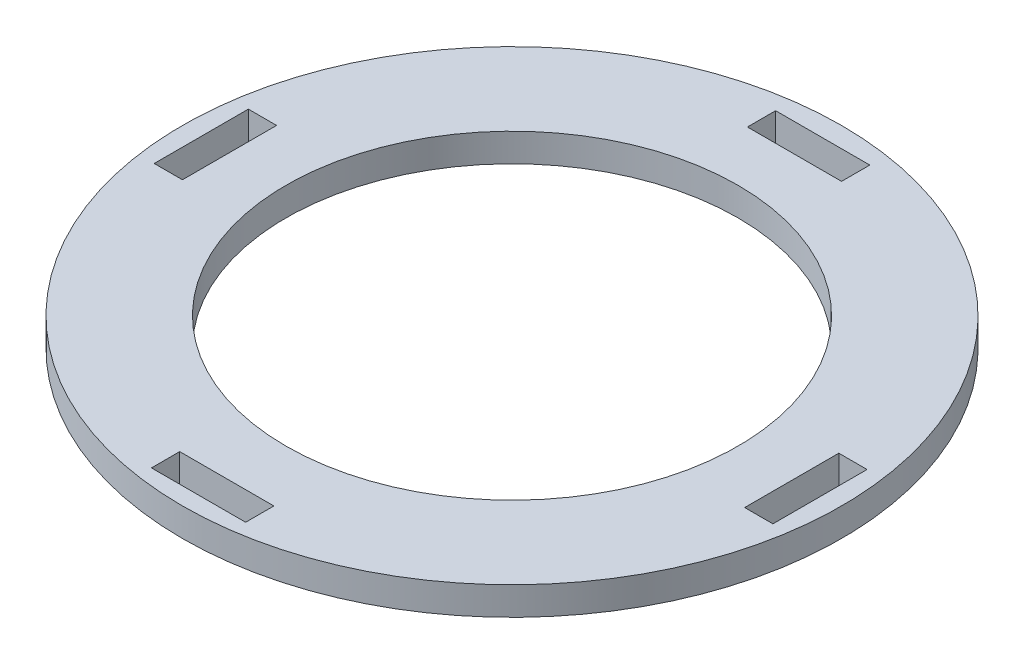
SolidWorks part; units mm, degrees
ref_plane "Přední rovina" through (0, 0, 0) normal (0, 0, 1) x (1, 0, 0)
ref_plane "Horní rovina" through (0, 0, 0) normal (0, 1, 0) x (1, 0, 0)
ref_plane "Pravá rovina" through (0, 0, 0) normal (1, 0, 0) x (0, 0, -1)
sketch "Skica1" plane through (0, 0, 0) normal (0, 1, 0) x (1, 0, 0)
  circle A0 centre (0, 0) radius 35
  dimension "D1" = 70
extrude "Přidat vysunutím1" add sketch "Skica1" along normal blind 3
sketch "Skica2" plane through (0, 3, 0) normal (0, 1, 0) x (1, 0, 0)
  circle A0 centre (0, 0) radius 24
  dimension "D1" = 48
extrude "Odebrat vysunutím1" cut sketch "Skica2" against normal blind 3
sketch "Skica3" plane through (0, 3, 0) normal (0, 1, 0) x (1, 0, 0)
  line L0 (38.0991, 0) -> (-38.2738, 0) construction
  line L1 (5.1452, 32.8548) -> (-4.8548, 32.8548)
  line L2 (-33, 5) -> (-30, 5)
  line L3 (-33, 5) -> (-33, -5)
  line L4 (-33, -5) -> (-30, -5)
  line L5 (-30, 5) -> (-30, -5)
  line L6 (-33, 5) -> (-30, -5) construction
  line L7 (-33, -5) -> (-30, 5) construction
  line L8 (5.1452, 32.8548) -> (5.1452, 29.8548)
  line L9 (5.1452, 29.8548) -> (-4.8548, 29.8548)
  line L10 (-4.8548, 32.8548) -> (-4.8548, 29.8548)
  line L11 (33, -5.2904) -> (33, 4.7096)
  line L12 (33, -5.2904) -> (30, -5.2904)
  line L13 (30, -5.2904) -> (30, 4.7096)
  line L14 (33, 4.7096) -> (30, 4.7096)
  line L15 (-5.1452, -33.1452) -> (4.8548, -33.1452)
  line L16 (-5.1452, -33.1452) -> (-5.1452, -30.1452)
  line L17 (-5.1452, -30.1452) -> (4.8548, -30.1452)
  line L18 (4.8548, -33.1452) -> (4.8548, -30.1452)
  point P3 (-31.5, 0)
  point P23 (0, -0.1452)
  dimension "D1" = 3
  dimension "D2" = 30
  dimension "D4" = 10
  dimension "D3" = 4
extrude "Odebrat vysunutím3" cut sketch "Skica3" against normal blind 3 contours L15 L18 L17 L16 | L11 L14 L13 L12 | L1 L10 L9 L8 | L3 L2 L5 L4 region at (0.1452, 3, -31.3548) region at (31.5, 3, 0.2904) region at (-0.1452, 3, 31.6452)
